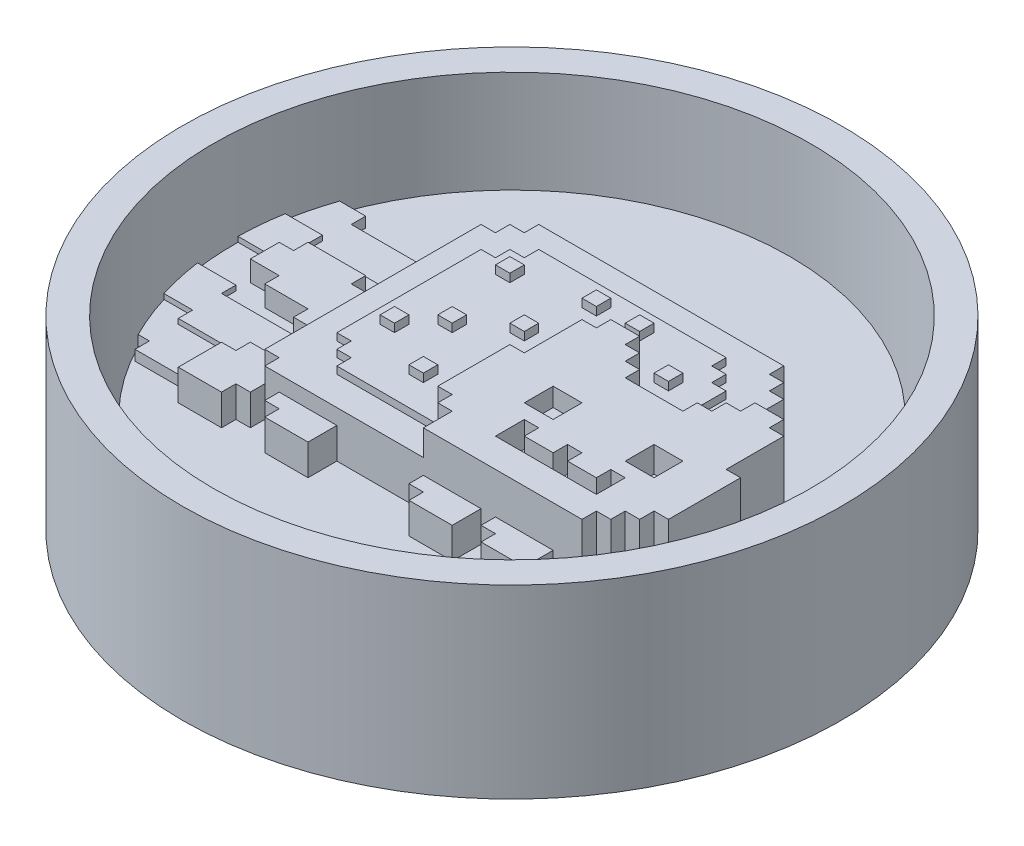
SolidWorks part; units mm, degrees
note: The reader was unsure of these and kept them because the rebuilt part matched: shared geometry of "Sketch15<2>".
ref_plane "Front Plane" through (0, 0, 0) normal (0, 0, 1) x (1, 0, 0)
ref_plane "Top Plane" through (0, 0, 0) normal (0, 1, 0) x (1, 0, 0)
ref_plane "Right Plane" through (0, 0, 0) normal (1, 0, 0) x (0, 0, -1)
sketch "Sketch1" [suppressed] plane through (0, 0, 0) normal (0, 1, 0) x (1, 0, 0)
sketch "face" plane through (0, 0, 0) normal (0, 1, 0) x (1, 0, 0)
  line L0 (103.124, 88.9) -> (110.236, 88.9)
  line L1 (110.236, 88.9) -> (110.236, 85.344)
  line L2 (110.236, 85.344) -> (113.792, 85.344)
  line L3 (113.792, 85.344) -> (113.792, 81.788)
  line L4 (113.792, 81.788) -> (117.348, 81.788)
  line L5 (117.348, 81.788) -> (117.348, 78.232)
  line L6 (117.348, 78.232) -> (131.572, 78.232)
  line L7 (131.572, 78.232) -> (131.572, 81.788)
  line L8 (131.572, 81.788) -> (135.128, 81.788)
  line L9 (135.128, 81.788) -> (135.128, 85.344)
  line L10 (135.128, 85.344) -> (138.684, 85.344)
  line L11 (138.684, 85.344) -> (138.684, 88.9)
  line L12 (138.684, 88.9) -> (145.796, 88.9)
  line L13 (145.796, 88.9) -> (145.796, 85.344)
  line L14 (145.796, 85.344) -> (149.352, 85.344)
  line L15 (149.352, 85.344) -> (149.352, 71.12)
  line L16 (149.352, 71.12) -> (152.908, 71.12)
  line L17 (152.908, 71.12) -> (152.908, 53.34)
  line L18 (152.908, 53.34) -> (149.352, 53.34)
  line L19 (149.352, 53.34) -> (149.352, 49.784)
  line L20 (149.352, 49.784) -> (145.796, 49.784)
  line L21 (145.796, 49.784) -> (145.796, 46.228)
  line L22 (145.796, 46.228) -> (142.24, 46.228)
  line L23 (142.24, 46.228) -> (142.24, 42.672)
  line L24 (142.24, 42.672) -> (103.124, 42.672)
  line L25 (103.124, 42.672) -> (103.124, 49.784)
  line L26 (103.124, 49.784) -> (99.568, 49.784)
  line L27 (99.568, 49.784) -> (99.568, 53.34)
  line L28 (99.568, 53.34) -> (96.012, 53.34)
  line L29 (96.012, 53.34) -> (96.012, 71.12)
  line L30 (96.012, 71.12) -> (99.568, 71.12)
  line L31 (99.568, 71.12) -> (99.568, 85.344)
  line L32 (99.568, 85.344) -> (103.124, 85.344)
  line L33 (110.236, 67.564) -> (110.236, 60.452)
  line L34 (110.236, 60.452) -> (117.348, 60.452)
  line L35 (117.348, 60.452) -> (117.348, 67.564)
  line L36 (117.348, 67.564) -> (110.236, 67.564)
  line L37 (135.128, 67.564) -> (135.128, 60.452)
  line L38 (135.128, 60.452) -> (142.24, 60.452)
  line L39 (142.24, 60.452) -> (142.24, 67.564)
  line L40 (142.24, 67.564) -> (135.128, 67.564)
  line L41 (113.792, 56.896) -> (113.792, 49.784)
  line L42 (113.792, 49.784) -> (138.684, 49.784)
  line L43 (138.684, 49.784) -> (138.684, 56.896)
  line L44 (138.684, 56.896) -> (135.128, 56.896)
  line L45 (135.128, 56.896) -> (135.128, 53.34)
  line L46 (135.128, 53.34) -> (128.016, 53.34)
  line L47 (128.016, 53.34) -> (128.016, 56.896)
  line L48 (128.016, 56.896) -> (124.46, 56.896)
  line L49 (124.46, 56.896) -> (124.46, 53.34)
  line L50 (124.46, 53.34) -> (117.348, 53.34)
  line L51 (117.348, 53.34) -> (117.348, 56.896)
  line L52 (117.348, 56.896) -> (113.792, 56.896)
  line L53 (103.124, 88.9) -> (103.124, 85.344)
sketch "poptart" plane through (0, 0, 0) normal (0, 1, 0) x (1, 0, 0)
  line L1 (135.128, 99.568) -> (131.572, 99.568)
  line L2 (131.572, 99.568) -> (131.572, 103.124)
  line L3 (131.572, 103.124) -> (128.016, 103.124)
  line L4 (128.016, 103.124) -> (128.016, 106.68)
  line L5 (128.016, 106.68) -> (67.564, 106.68)
  line L6 (67.564, 106.68) -> (67.564, 103.124)
  line L7 (67.564, 103.124) -> (64.008, 103.124)
  line L8 (64.008, 103.124) -> (64.008, 99.568)
  line L9 (64.008, 99.568) -> (60.452, 99.568)
  line L10 (60.452, 99.568) -> (60.452, 46.228)
  line L11 (60.452, 46.228) -> (64.008, 46.228)
  line L12 (64.008, 46.228) -> (64.008, 42.672)
  line L13 (64.008, 42.672) -> (135.128, 42.672)
  line L14 (142.24, 42.672) -> (103.124, 42.672) construction
  line L15 (135.128, 42.672) -> (145.796, 53.34)
  line L16 (145.796, 53.34) -> (145.796, 71.12)
  line L17 (145.796, 71.12) -> (135.128, 85.344)
  line L18 (135.128, 85.344) -> (135.128, 99.568)
sketch "feet tail" plane through (0, 0, 0) normal (0, 1, 0) x (1, 0, 0)
  line L0 (60.452, 74.676) -> (53.34, 74.676)
  line L1 (60.452, 99.568) -> (60.452, 46.228) construction
  line L2 (53.34, 74.676) -> (53.34, 78.232)
  line L3 (53.34, 78.232) -> (39.116, 78.232)
  line L4 (39.116, 78.232) -> (39.116, 74.676)
  line L5 (39.116, 74.676) -> (35.56, 74.676)
  line L6 (35.56, 74.676) -> (35.56, 67.564)
  line L7 (35.56, 67.564) -> (42.672, 67.564)
  line L8 (42.672, 67.564) -> (42.672, 64.008)
  line L9 (42.672, 64.008) -> (53.34, 64.008)
  line L10 (53.34, 64.008) -> (53.34, 60.452)
  line L11 (53.34, 60.452) -> (60.452, 60.452)
  line L12 (60.452, 60.452) -> (60.452, 74.676)
  line L13 (60.452, 53.34) -> (56.896, 53.34)
  line L14 (56.896, 53.34) -> (56.896, 49.784)
  line L15 (56.896, 49.784) -> (53.34, 49.784)
  line L16 (53.34, 49.784) -> (53.34, 46.228)
  line L17 (53.34, 46.228) -> (49.784, 46.228)
  line L18 (49.784, 46.228) -> (49.784, 35.56)
  line L19 (49.784, 35.56) -> (60.452, 35.56)
  line L20 (60.452, 35.56) -> (60.452, 39.116)
  line L21 (60.452, 39.116) -> (64.008, 39.116)
  line L22 (64.008, 39.116) -> (64.008, 46.228)
  line L23 (67.564, 42.672) -> (67.564, 39.116)
  line L24 (64.008, 42.672) -> (135.128, 42.672) construction
  line L25 (67.564, 39.116) -> (71.12, 39.116)
  line L26 (71.12, 39.116) -> (71.12, 35.56)
  line L27 (71.12, 35.56) -> (81.788, 35.56)
  line L28 (81.788, 35.56) -> (81.788, 42.672)
  line L29 (81.788, 42.672) -> (67.564, 42.672)
  line L30 (64.008, 46.228) -> (60.452, 46.228)
  line L31 (60.452, 46.228) -> (60.452, 53.34)
  line L33 (103.124, 42.672) -> (103.124, 39.116)
  line L34 (103.124, 39.116) -> (106.68, 39.116)
  line L35 (106.68, 39.116) -> (106.68, 35.56)
  line L36 (106.68, 35.56) -> (117.348, 35.56)
  line L37 (117.348, 35.56) -> (117.348, 42.672)
  line L38 (142.24, 42.672) -> (103.124, 42.672) construction
  line L39 (117.348, 42.672) -> (103.124, 42.672)
  line L40 (120.904, 42.672) -> (120.904, 39.116)
  line L41 (120.904, 39.116) -> (124.46, 39.116)
  line L42 (124.46, 39.116) -> (124.46, 35.56)
  line L43 (124.46, 35.56) -> (135.128, 35.56)
  line L44 (135.128, 35.56) -> (135.128, 42.672)
  line L45 (135.128, 42.672) -> (120.904, 42.672)
sketch "sprinkles" plane through (0, 0, 0) normal (0, 1, 0) x (1, 0, 0)
  line L1 (71.12, 67.564) -> (74.676, 67.564)
  line L2 (71.12, 67.564) -> (71.12, 64.008)
  line L3 (71.12, 64.008) -> (74.676, 64.008)
  line L4 (74.676, 67.564) -> (74.676, 64.008)
  line L5 (78.232, 74.676) -> (81.788, 74.676)
  line L6 (78.232, 74.676) -> (78.232, 71.12)
  line L7 (78.232, 71.12) -> (81.788, 71.12)
  line L8 (81.788, 74.676) -> (81.788, 71.12)
  line L9 (88.9, 81.788) -> (92.456, 81.788)
  line L10 (88.9, 81.788) -> (88.9, 78.232)
  line L11 (88.9, 78.232) -> (92.456, 78.232)
  line L12 (92.456, 81.788) -> (92.456, 78.232)
  line L13 (74.676, 92.456) -> (78.232, 92.456)
  line L14 (74.676, 92.456) -> (74.676, 88.9)
  line L15 (74.676, 88.9) -> (78.232, 88.9)
  line L16 (78.232, 92.456) -> (78.232, 88.9)
  line L17 (92.456, 96.012) -> (96.012, 96.012)
  line L18 (92.456, 96.012) -> (92.456, 92.456)
  line L19 (92.456, 92.456) -> (96.012, 92.456)
  line L20 (96.012, 96.012) -> (96.012, 92.456)
  line L21 (103.124, 96.012) -> (106.68, 96.012)
  line L22 (103.124, 96.012) -> (103.124, 92.456)
  line L23 (103.124, 92.456) -> (106.68, 92.456)
  line L24 (106.68, 96.012) -> (106.68, 92.456)
  line L25 (117.348, 88.9) -> (120.904, 88.9)
  line L26 (117.348, 88.9) -> (117.348, 85.344)
  line L27 (117.348, 85.344) -> (120.904, 85.344)
  line L28 (120.904, 88.9) -> (120.904, 85.344)
  line L29 (85.344, 60.452) -> (88.9, 60.452)
  line L30 (85.344, 60.452) -> (85.344, 56.896)
  line L31 (85.344, 56.896) -> (88.9, 56.896)
  line L32 (88.9, 60.452) -> (88.9, 56.896)
sketch "engrave poptart" plane through (0, 0, 0) normal (0, 1, 0) x (1, 0, 0)
  line L0 (71.12, 53.34) -> (74.676, 53.34)
  line L1 (74.676, 53.34) -> (74.676, 49.784)
  line L2 (74.676, 49.784) -> (99.8163, 49.76)
  line L3 (71.12, 53.34) -> (71.12, 56.896)
  line L4 (71.12, 56.896) -> (67.564, 56.896)
  line L5 (67.564, 56.896) -> (67.564, 92.456)
  line L6 (67.564, 92.456) -> (71.12, 92.456)
  line L7 (71.12, 92.456) -> (71.12, 96.012)
  line L8 (71.12, 96.012) -> (74.676, 96.012)
  line L9 (74.676, 96.012) -> (74.676, 99.568)
  line L10 (74.676, 99.568) -> (120.904, 99.568)
  line L11 (120.904, 99.568) -> (120.904, 96.012)
  line L12 (120.904, 96.012) -> (124.46, 96.012)
  line L13 (124.46, 96.012) -> (124.46, 92.456)
  line L14 (124.46, 92.456) -> (128.016, 92.456)
  line L15 (128.016, 92.456) -> (128.016, 67.564)
  line L16 (128.016, 67.564) -> (128.016, 64.008)
  line L17 (128.016, 64.008) -> (99.568, 49.784)
  line L18 (99.568, 49.784) -> (99.8163, 49.76)
extrude "face-" add sketch "face" along normal blind 17.78
extrude "feettail" add sketch "feet tail" along normal blind 7.62
extrude "poptart-" add sketch "poptart" along normal blind 11.43
extrude "sprinkle" add sketch "sprinkles" along normal blind 15.24
extrude "engrave" add sketch "engrave poptart" along normal blind 13.208
sketch "Sketch2" plane through (0, 0, 0) normal (0, 1, 0) x (1, 0, 0)
  circle A0 centre (93.98, 73.66) radius 68.58
sketch "Sketch4" plane through (0, 0, 0) normal (0, 1, 0) x (1, 0, 0)
  circle A0 centre (93.98, 73.66) radius 157.48
  circle A1 centre (93.98, 73.66) radius 81.28 construction
  circle A2 centre (93.98, 73.66) radius 73.66
  dimension "D1" = 76.2
extrude "CUPCAKE" add sketch "Sketch2" against normal blind 15.24
extrude "retaining" add sketch "Sketch4" against normal blind 45.72 from offset 21.59
sketch "Sketch5" plane through (0, 0, 0) normal (0, 1, 0) x (1, 0, 0)
  circle A1 centre (93.98, 73.66) radius 81.28
extrude "cupcake body" add sketch "Sketch5" against normal blind 6.35 from offset 17.78 offset against normal yes
sketch "Sketch10" plane through (0, 0, 0) normal (0, 1, 0) x (1, 0, 0)
  line L0 (60.452, 92.456) -> (35.56, 92.456)
  line L1 (35.56, 92.456) -> (35.56, 96.012)
  line L2 (35.56, 96.012) -> (29.1448, 96.012)
  line L4 (26.4026, 85.344) -> (35.56, 85.344)
  line L5 (35.56, 85.344) -> (35.56, 81.788)
  line L6 (35.56, 81.788) -> (60.452, 81.788)
  line L7 (60.452, 81.788) -> (60.452, 92.456)
  line L8 (35.56, 74.676) -> (25.4075, 74.676)
  line L14 (26.0826, 64.008) -> (35.56, 64.008)
  line L15 (35.56, 64.008) -> (35.56, 60.452)
  line L16 (35.56, 60.452) -> (53.34, 60.452)
  line L17 (53.34, 60.452) -> (53.34, 64.008)
  line L18 (53.34, 64.008) -> (42.672, 64.008)
  line L19 (42.672, 64.008) -> (42.672, 67.564)
  line L20 (42.672, 67.564) -> (35.56, 67.564)
  line L21 (35.56, 74.676) -> (35.56, 67.564) construction
  line L22 (35.56, 67.564) -> (42.672, 67.564) construction
  line L23 (35.56, 67.564) -> (35.56, 74.676)
  line L24 (53.34, 49.784) -> (35.56, 49.784)
  line L25 (35.56, 49.784) -> (35.56, 53.34)
  line L26 (35.56, 53.34) -> (28.4795, 53.34)
  line L28 (32.8003, 42.672) -> (35.56, 42.672)
  line L29 (35.56, 42.672) -> (35.56, 39.116)
  line L30 (35.56, 39.116) -> (49.784, 39.116)
  line L31 (49.784, 39.116) -> (49.784, 46.228)
  line L32 (49.784, 46.228) -> (53.34, 46.228)
  line L33 (53.34, 46.228) -> (53.34, 49.784)
  arc A0 (29.1448, 96.012) -> (26.4026, 85.344) centre (93.98, 73.66) ccw
  arc A1 (28.4795, 53.34) -> (32.8003, 42.672) centre (93.98, 73.66) ccw
  arc A2 (25.4075, 74.676) -> (26.0826, 64.008) centre (93.98, 73.66) ccw
extrude "Boss-Extrude1" add sketch "Sketch10" along normal blind 2.54
sketch "Sketch11" plane through (0, 0, 0) normal (0, 1, 0) x (1, 0, 0)
  line L0 (26.0826, 64.008) -> (35.56, 64.008)
  line L1 (35.56, 64.008) -> (35.56, 60.452)
  line L2 (35.56, 60.452) -> (60.452, 60.452)
  line L3 (35.56, 60.452) -> (60.452, 60.452) construction
  line L4 (60.452, 60.452) -> (60.452, 53.34)
  line L5 (60.452, 53.34) -> (56.896, 53.34)
  line L6 (56.896, 53.34) -> (56.896, 49.784)
  line L7 (56.896, 53.34) -> (56.896, 49.784) construction
  line L8 (56.896, 53.34) -> (56.896, 49.784) construction
  line L9 (56.896, 49.784) -> (35.56, 49.784)
  line L10 (35.56, 49.784) -> (35.56, 53.34)
  line L11 (35.56, 53.34) -> (28.4795, 53.34)
  line L12 (60.452, 81.788) -> (60.452, 74.676)
  line L13 (60.452, 74.676) -> (53.34, 74.676)
  line L14 (53.34, 74.676) -> (53.34, 78.232)
  line L15 (53.34, 74.676) -> (53.34, 78.232) construction
  line L16 (53.34, 78.232) -> (39.116, 78.232) construction
  line L17 (53.34, 78.232) -> (39.116, 78.232)
  line L18 (39.116, 78.232) -> (39.116, 74.676)
  line L19 (7.112, 74.676) -> (53.34, 74.676) construction
  line L20 (39.116, 78.232) -> (39.116, 74.676) construction
  line L21 (39.116, 74.676) -> (25.4075, 74.676)
  line L22 (26.4026, 85.344) -> (35.56, 85.344)
  line L24 (35.56, 85.344) -> (35.56, 81.788)
  line L25 (35.56, 81.788) -> (60.452, 81.788)
  arc A0 (26.4026, 85.344) -> (25.4075, 74.676) centre (93.98, 73.66) ccw
  arc A1 (26.0826, 64.008) -> (28.4795, 53.34) centre (93.98, 73.66) ccw
extrude "Boss-Extrude2" add sketch "Sketch11" along normal blind 3.81
sketch "Sketch15" plane through (0, 21.59, 0) normal (0, 1, 0) x (-1, 0, 0)
  circle A0 centre (-93.98, -73.66) radius 157.48
  circle A1 centre (-93.98, -73.66) radius 81.28
  dimension "D1" = 76.2
extrude "Boss-Extrude4" add sketch "Sketch15" against normal through all
extrude "Cut-Extrude1" cut sketch "Sketch15<2>" against normal through all
sketch "Sketch15<2>" plane through (0, 21.59, 0) normal (0, 1, 0) x (-1, 0, 0) same geometry as "Sketch15"
